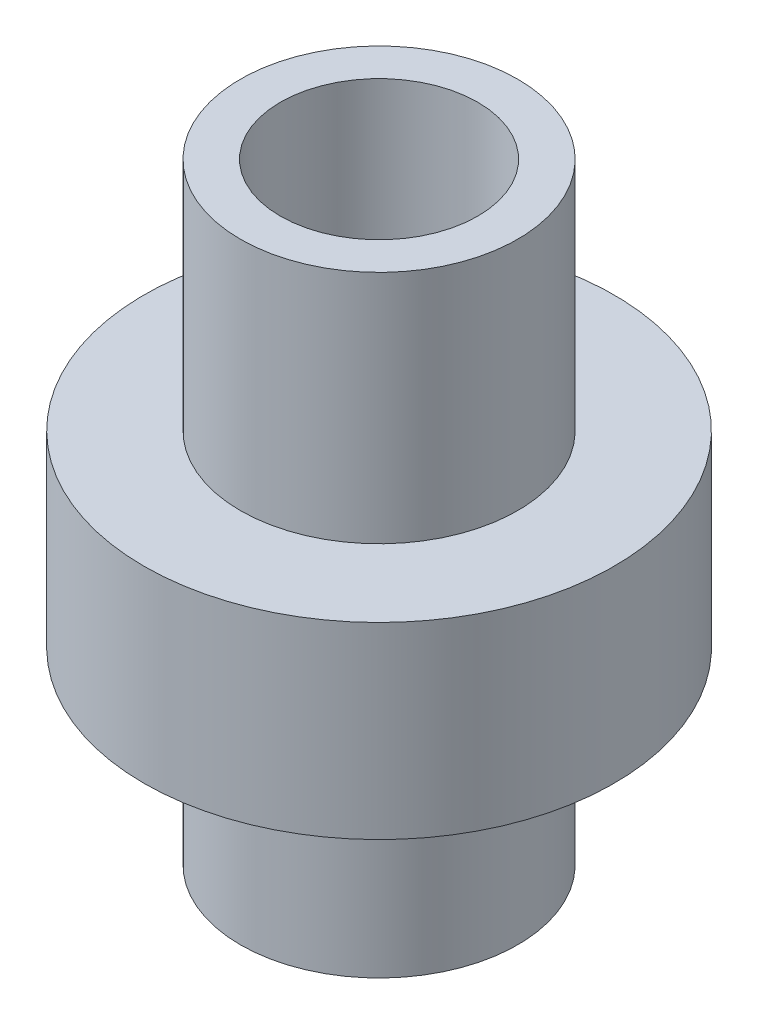
SolidWorks part; units mm, degrees
ref_plane "Front Plane" through (0, 0, 0) normal (0, 0, 1) x (1, 0, 0)
ref_plane "Top Plane" through (0, 0, 0) normal (0, 1, 0) x (1, 0, 0)
ref_plane "Right Plane" through (0, 0, 0) normal (1, 0, 0) x (0, 0, -1)
sketch "Sketch1" plane through (0, 0, 0) normal (0, 1, 0) x (1, 0, 0)
  line L0 (-9.7616, 0) -> (9.5995, 0) construction
  line L1 (0, 6.2136) -> (0, -6.2316) construction
  circle A0 centre (0, 0) radius 1.475
  circle A1 centre (0, 0) radius 1.05
  dimension "D1" = 2.95
  dimension "D2" = 2.1
extrude "Boss-Extrude1" add sketch "Sketch1" along normal blind 2
sketch "Sketch2" plane through (0, 2, 0) normal (0, 1, 0) x (1, 0, 0)
  circle A0 centre (0, 0) radius 2.5
  circle A1 centre (0, 0) radius 1.05
  circle M4 centre (0, 0) radius 1.05
  dimension "D1" = 2.1
  dimension "D2" = 5
extrude "Boss-Extrude2" add sketch "Sketch2" along normal blind 2 contours M4 | A0 region at (0, 2, 0)
sketch "Sketch4" plane through (0, 4, 0) normal (0, 1, 0) x (1, 0, 0)
  circle A0 centre (0, 0) radius 1.05
  circle A1 centre (0, 0) radius 1.475
  dimension "D1" = 2.1
  dimension "D2" = 2.95
extrude "Boss-Extrude3" add sketch "Sketch4" along normal blind 2.5
